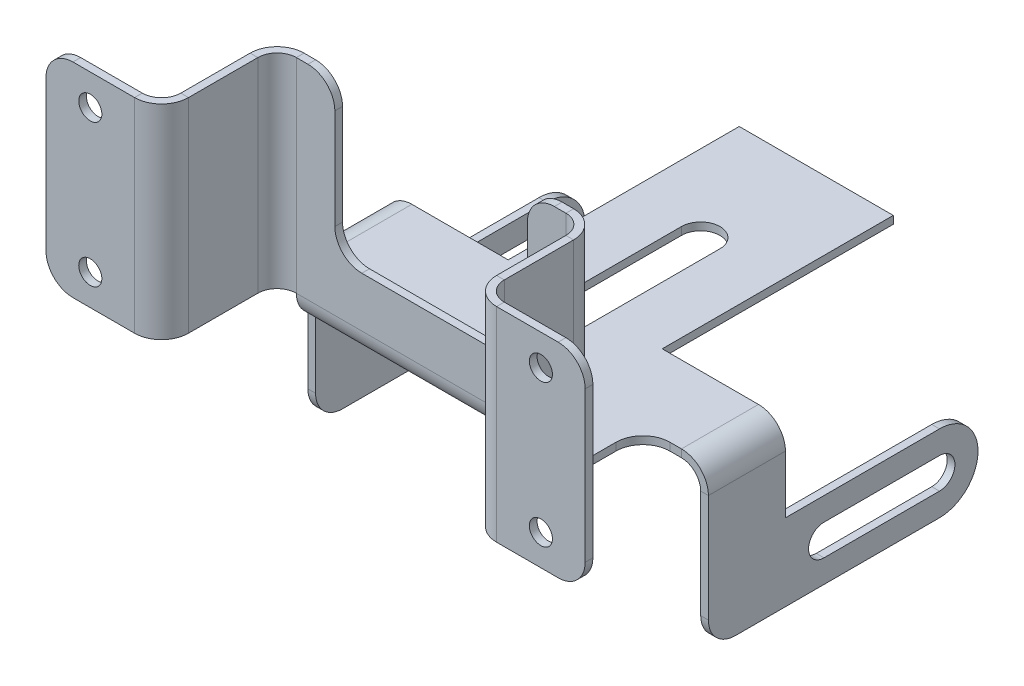
SolidWorks part; units mm, degrees
note: The reader was unsure of these and kept them because the rebuilt part matched: flange length of "边线-法兰1", "边线-法兰3", "边线-法兰4", "边线-法兰5".
ref_plane "前视基准面" through (0, 0, 0) normal (0, 0, 1) x (1, 0, 0)
ref_plane "上视基准面" through (0, 0, 0) normal (0, 1, 0) x (1, 0, 0)
ref_plane "右视基准面" through (0, 0, 0) normal (1, 0, 0) x (0, 0, -1)
other "Configuration Table"
sketch "草图1" plane through (0, 0, 0) normal (0, 0, 1) x (1, 0, 0)
  line L0 (-25, 0) -> (25, 0)
  dimension "D1" = 50
base flange "基体-法兰1" sketch "草图1" end condition mid plane depth 10 reverse direction no thickness 1 reverse thickness direction no bend radius 2.5
edge flange "边线-法兰1" sketch "草图8" flange angle 90 flange length 21 flange position material outside bend radius 2.5 thickness 1 parameters "D6"=10
sketch "草图8" plane through (-25, -1, 0) normal (-1, 0, 0) x (0, 0, -1)
  line L2 (-5, 0) -> (-5, 20)
  line L3 (-5, 20) -> (5, 20)
  line L4 (5, 20) -> (5, 0)
  line L7 (-5, 0) -> (5, 0) construction
  line L8 (-5, 0) -> (5, 0)
  dimension "D1" = 20
bend "边线折弯1" bend radius 2.5 bend angle 90 parameters "D5"=1
sketch "草图9" plane through (-26, 0, 0) normal (-1, 0, 0) x (0, 0, 1)
  line L0 (-5, -16) -> (-25, -16) construction
  line L1 (-5, -3.5) -> (-5, -21) construction
  line L2 (-5, -21) -> (-25, -21)
  line L3 (-5, -11) -> (-25, -11)
  line L4 (-5, -21) -> (5, -21) construction
  line L5 (-5, -11) -> (-5, -21)
  line L6 (-10, -16) -> (-25, -16) construction
  line L7 (-10, -18) -> (-25, -18)
  line L8 (-10, -14) -> (-25, -14)
  arc A0 (-5, -21) -> (-5, -11) centre (-5, -16) ccw construction
  arc A1 (-25, -11) -> (-25, -21) centre (-25, -16) ccw
  arc A2 (-10, -18) -> (-10, -14) centre (-10, -16) ccw
  arc A3 (-25, -14) -> (-25, -18) centre (-25, -16) ccw
  point P11 (-17.5, -16)
  dimension "D2" = 5
  dimension "D3" = 5
  dimension "D5" = 2
  dimension "D1" = 20
  dimension "D4" = 10
  dimension "D6" = 15
base flange "薄片1" sketch "草图9" thickness 1 reverse thickness direction no parameters "D1"=2.5
mirror "镜向1" about plane through (0, 0, 0) normal (1, 0, 0) of "薄片1", "边线-法兰1"
bend "镜向折弯1" bend radius 2.5 bend angle 90 parameters "D5"=2
sketch "草图12" plane through (0, -1, 0) normal (0, -1, 0) x (1, 0, 0)
  line L0 (-22.5, -5) -> (22.5, -5) construction
  line L1 (-10, -5) -> (10, -5)
  line L2 (-10, -5) -> (-10, -35)
  line L3 (-10, -35) -> (10, -35)
  line L4 (10, -5) -> (10, -35)
  line L5 (-10, -5) -> (10, -35) construction
  line L6 (-10, -35) -> (10, -5) construction
  line L7 (-22.5, 5) -> (22.5, 5) construction
  line L8 (-17.5, 15) -> (17.5, 15)
  line L9 (-17.5, 15) -> (-17.5, 5)
  line L10 (-17.5, 5) -> (17.5, 5)
  line L11 (17.5, 15) -> (17.5, 5)
  line L12 (-17.5, 15) -> (17.5, 5) construction
  line L13 (-17.5, 5) -> (17.5, 15) construction
  point P0 (0, -20)
  point P10 (0, 10)
  dimension "D1" = 30
  dimension "D2" = 20
  dimension "D3" = 35
  dimension "D4" = 10
base flange "薄片2" sketch "草图12" thickness 1 reverse thickness direction no parameters "D1"=2.5
edge flange "边线-法兰3" sketch "草图20" flange angle 90 flange length 30 flange position material inside bend radius 2.5 thickness 1 parameters "D6"=10
sketch "草图20" plane through (0, 0, 15) normal (0, 0, 1) x (1, 0, 0)
  line L2 (-17.5, 0) -> (-17.5, 29)
  line L3 (-17.5, 29) -> (17.5, 29)
  line L4 (17.5, 29) -> (17.5, 0)
  line L7 (17.5, 0) -> (-17.5, 0) construction
  line L8 (17.5, 0) -> (-17.5, 0)
bend "边线折弯3" bend radius 2.5 bend angle 90 parameters "D5"=3
sketch "草图21" plane through (0, 0, 15) normal (0, 0, 1) x (1, 0, 0)
  line L0 (17.5, 29) -> (-17.5, 29) construction
  line L1 (-12.5, 29) -> (12.5, 29)
  line L2 (-12.5, 29) -> (-12.5, 9)
  line L3 (-12.5, 9) -> (12.5, 9)
  line L4 (12.5, 29) -> (12.5, 9)
  line L5 (-12.5, 29) -> (12.5, 9) construction
  line L6 (-12.5, 9) -> (12.5, 29) construction
  point P0 (0, 19)
  dimension "D1" = 25
  dimension "D2" = 20
extrude "切除-拉伸1" cut sketch "草图21" against normal up to next
edge flange "边线-法兰4" sketch "草图24" flange angle 90 flange length 15 flange position bend outside bend radius 2.5 thickness 1 parameters "D6"=10
sketch "草图24" plane through (-17.5, 0, 15) normal (-1, 0, 0) x (0, -1, 0)
  line L2 (-29, 0) -> (-29, 14)
  line L3 (-29, 14) -> (-2.5, 14)
  line L4 (-2.5, 14) -> (-2.5, 0)
  line L7 (-29, 0) -> (-2.5, 0) construction
  line L8 (-29, 0) -> (-2.5, 0)
bend "边线折弯4" bend radius 2.5 bend angle 90 parameters "D5"=4
edge flange "边线-法兰5" sketch "草图27" flange angle 90 flange length 15 flange position material outside bend radius 2.5 thickness 1 parameters "D6"=10
sketch "草图27" plane through (-21, 0, 29) normal (0, 0, 1) x (0, 1, 0)
  line L0 (2.5, 0) -> (29, 0) construction
  line L1 (2.5, 0) -> (29, 0)
  line L2 (2.5, 0) -> (2.5, 14)
  line L3 (2.5, 14) -> (29, 14)
  line L4 (29, 14) -> (29, 0)
bend "边线折弯5" bend radius 2.5 bend angle 90 parameters "D5"=5
sketch "草图28" plane through (0, 0, 30) normal (0, 0, 1) x (1, 0, 0)
  line L0 (-23.5, 29) -> (-35, 29) construction
  line L1 (-35, 15.75) -> (-23.5, 15.75) construction
  line L2 (-35, 29) -> (-35, 2.5) construction
  line L3 (-23.5, 29) -> (-23.5, 2.5) construction
  circle A0 centre (-29.25, 25) radius 1.5
  circle A1 centre (-29.25, 6.5) radius 1.5
  point P5 (-29.25, 29)
  dimension "D1" = 3
  dimension "D2" = 4
extrude "切除-拉伸2" cut sketch "草图28" against normal up to next
mirror "镜向2" about plane through (0, 0, 0) normal (1, 0, 0) of "切除-拉伸2", "边线-法兰4", "边线-法兰5"
bend "镜向折弯2" bend radius 2.5 bend angle 90 parameters "D5"=6
bend "镜向折弯3" bend radius 2.5 bend angle 90 parameters "D5"=7
fillet "圆角1" radius 3.5 12 edges at (17.5, -0.5, 5) (-17.5, -0.5, 5) (12.5, 29, 14.5) (12.5, 9, 14.5) (-12.5, 9, 14.5) (-12.5, 29, 14.5) (-35, 2.5, 29.5) (-35, 29, 29.5) (35, 29, 29.5) (35, 2.5, 29.5) (-25.5, -21, 5) (25.5, -21, 5)
sketch "草图29" plane through (0, -1, 0) normal (0, -1, 0) x (1, 0, 0)
  line L0 (0, 0) -> (0, -20) construction
  line L1 (2.5, 0) -> (2.5, -20)
  line L2 (-2.5, 0) -> (-2.5, -20)
  arc A0 (2.5, 0) -> (-2.5, 0) centre (0, 0) ccw
  arc A1 (-2.5, -20) -> (2.5, -20) centre (0, -20) ccw
  point P2 (0, -10)
  point P7 (0, 0)
  dimension "D1" = 20
  dimension "D2" = 5
extrude "切除-拉伸3" cut sketch "草图29" against normal up to next
sketch "折弯-线1" [suppressed] plane through (0, 0, 0) normal (0, 1, 0) x (1, 0, 0)
sketch "边界框1" [suppressed] plane through (0, 0, 0) normal (0, 1, 0) x (1, 0, 0)
sheet metal parameters "钣金6" thickness 1 parameters "D1"=2.5
flat pattern "平板型式6" [suppressed]
sketch "折弯-线2" plane through (0, 0, 0) normal (0, 1, 0) x (1, 0, 0)
sketch "边界框2" [suppressed] plane through (0, 0, 0) normal (0, 1, 0) x (1, 0, 0)
sheet metal parameters "钣金7" thickness 1 parameters "D1"=2.5
flat pattern "平板型式6" [suppressed]
sketch "折弯-线2" plane through (0, 0, 0) normal (0, 1, 0) x (1, 0, 0)
sketch "边界框2" [suppressed] plane through (0, 0, 0) normal (0, 1, 0) x (1, 0, 0)
bend of the flat pattern "展平-<边线折弯1>1"
sheet metal parameters "钣金8" thickness 1 parameters "D1"=2.5
flat pattern "平板型式8" [suppressed]
sketch "折弯-线3" plane through (0, 0, 0) normal (0, 1, 0) x (1, 0, 0)
sketch "边界框3" [suppressed] plane through (0, 0, 0) normal (0, 1, 0) x (1, 0, 0)
bend of the flat pattern "展平-<边线折弯1>2"
sheet metal parameters "钣金9" thickness 1 parameters "D1"=2.5
flat pattern "平板型式8" [suppressed]
sketch "折弯-线3" plane through (0, 0, 0) normal (0, 1, 0) x (1, 0, 0)
sketch "边界框3" [suppressed] plane through (0, 0, 0) normal (0, 1, 0) x (1, 0, 0)
bend of the flat pattern "展平-<边线折弯1>2"
bend of the flat pattern "展平-<镜向折弯1>1"
sheet metal parameters "钣金10" thickness 1 parameters "D1"=2.5
flat pattern "平板型式10" [suppressed]
sketch "折弯-线4" plane through (0, 0, 0) normal (0, 1, 0) x (1, 0, 0)
sketch "边界框4" [suppressed] plane through (0, 0, 0) normal (0, 1, 0) x (1, 0, 0)
bend of the flat pattern "展平-<边线折弯1>3"
bend of the flat pattern "展平-<镜向折弯1>2"
sheet metal parameters "钣金12" thickness 1 parameters "D1"=2.5
flat pattern "平板型式10" [suppressed]
sketch "折弯-线4" plane through (0, 0, 0) normal (0, 1, 0) x (1, 0, 0)
sketch "边界框4" [suppressed] plane through (0, 0, 0) normal (0, 1, 0) x (1, 0, 0)
bend of the flat pattern "展平-<边线折弯1>3"
bend of the flat pattern "展平-<镜向折弯1>2"
bend of the flat pattern "展平-<边线折弯3>1"
sheet metal parameters "钣金13" thickness 1 parameters "D1"=2.5
flat pattern "平板型式10" [suppressed]
sketch "折弯-线4" plane through (0, 0, 0) normal (0, 1, 0) x (1, 0, 0)
sketch "边界框4" [suppressed] plane through (0, 0, 0) normal (0, 1, 0) x (1, 0, 0)
bend of the flat pattern "展平-<边线折弯1>3"
bend of the flat pattern "展平-<镜向折弯1>2"
bend of the flat pattern "展平-<边线折弯3>1"
sheet metal parameters "钣金14" thickness 1 parameters "D1"=2.5
flat pattern "平板型式10" [suppressed]
sketch "折弯-线4" plane through (0, 0, 0) normal (0, 1, 0) x (1, 0, 0)
sketch "边界框4" [suppressed] plane through (0, 0, 0) normal (0, 1, 0) x (1, 0, 0)
bend of the flat pattern "展平-<边线折弯1>3"
bend of the flat pattern "展平-<镜向折弯1>2"
bend of the flat pattern "展平-<边线折弯3>1"
bend of the flat pattern "展平-<边线折弯4>1"
sheet metal parameters "钣金15" thickness 1 parameters "D1"=2.5
flat pattern "平板型式10" [suppressed]
sketch "折弯-线4" plane through (0, 0, 0) normal (0, 1, 0) x (1, 0, 0)
sketch "边界框4" [suppressed] plane through (0, 0, 0) normal (0, 1, 0) x (1, 0, 0)
bend of the flat pattern "展平-<边线折弯1>3"
bend of the flat pattern "展平-<镜向折弯1>2"
bend of the flat pattern "展平-<边线折弯3>1"
bend of the flat pattern "展平-<边线折弯4>1"
bend of the flat pattern "展平-<边线折弯5>1"
sheet metal parameters "钣金16" thickness 1 parameters "D1"=2.5
flat pattern "平板型式10" [suppressed]
sketch "折弯-线4" plane through (0, 0, 0) normal (0, 1, 0) x (1, 0, 0)
sketch "边界框4" [suppressed] plane through (0, 0, 0) normal (0, 1, 0) x (1, 0, 0)
bend of the flat pattern "展平-<边线折弯1>3"
bend of the flat pattern "展平-<镜向折弯1>2"
bend of the flat pattern "展平-<边线折弯3>1"
bend of the flat pattern "展平-<边线折弯4>1"
bend of the flat pattern "展平-<边线折弯5>1"
sheet metal parameters "钣金17" thickness 1 parameters "D1"=2.5
flat pattern "平板型式10"
sketch "折弯-线4" plane through (0, 0, 0) normal (0, 1, 0) x (1, 0, 0)
  line L0 (33.5686, -16.2124) -> (33.5686, -42.7124) construction
  line L1 (19.8562, -16.2124) -> (19.8562, -42.7124) construction
  line L2 (-33.5686, -42.7124) -> (-33.5686, -16.2124) construction
  line L3 (-19.8562, -42.7124) -> (-19.8562, -16.2124) construction
  line L4 (17.5, -13.8562) -> (-17.5, -13.8562) construction
  line L5 (24.8562, 5) -> (24.8562, -5) construction
  line L6 (-24.8562, -5) -> (-24.8562, 5) construction
  line L7 (33.5686, -16.2124) -> (33.5686, -42.7124) construction
  line L8 (19.8562, -16.2124) -> (19.8562, -42.7124) construction
  line L9 (-33.5686, -42.7124) -> (-33.5686, -16.2124) construction
  line L10 (-19.8562, -42.7124) -> (-19.8562, -16.2124) construction
  line L11 (17.5, -13.8562) -> (-17.5, -13.8562) construction
  line L12 (24.8562, 5) -> (24.8562, -5) construction
  line L13 (-24.8562, -5) -> (-24.8562, 5) construction
sketch3d "边界框4" [suppressed]
  line L0 (-22.4248, -37.7123, 0) -> (72.4248, -37.7124, 0) construction
  line L1 (-22.4247, 40.0001, 0) -> (72.4249, 39.9999, 0) construction
  line L2 (-22.4248, -37.7123, 0) -> (-22.4247, 40.0001, 0) construction
  line L3 (72.4248, -37.7124, 0) -> (72.4249, 39.9999, 0) construction
bend of the flat pattern "展平-<边线折弯1>3"
bend of the flat pattern "展平-<镜向折弯1>2"
bend of the flat pattern "展平-<边线折弯3>1"
bend of the flat pattern "展平-<边线折弯4>1"
bend of the flat pattern "展平-<边线折弯5>1"
bend of the flat pattern "展平-<镜向折弯2>1"
bend of the flat pattern "展平-<镜向折弯3>1"
sheet metal parameters "钣金18" thickness 1 parameters "D1"=2.5
flat pattern "平板型式10"
sketch "折弯-线4" plane through (0, 0, 0) normal (0, 1, 0) x (1, 0, 0)
  line L0 (33.5686, -16.2124) -> (33.5686, -42.7124) construction
  line L1 (19.8562, -16.2124) -> (19.8562, -42.7124) construction
  line L2 (-33.5686, -42.7124) -> (-33.5686, -16.2124) construction
  line L3 (-19.8562, -42.7124) -> (-19.8562, -16.2124) construction
  line L4 (17.5, -13.8562) -> (-17.5, -13.8562) construction
  line L5 (24.8562, 5) -> (24.8562, -5) construction
  line L6 (-24.8562, -5) -> (-24.8562, 5) construction
  line L7 (33.5686, -16.2124) -> (33.5686, -42.7124) construction
  line L8 (19.8562, -16.2124) -> (19.8562, -42.7124) construction
  line L9 (-33.5686, -42.7124) -> (-33.5686, -16.2124) construction
  line L10 (-19.8562, -42.7124) -> (-19.8562, -16.2124) construction
  line L11 (17.5, -13.8562) -> (-17.5, -13.8562) construction
  line L12 (24.8562, 5) -> (24.8562, -5) construction
  line L13 (-24.8562, -5) -> (-24.8562, 5) construction
sketch3d "边界框4" [suppressed]
  line L0 (-22.4248, -37.7123, 0) -> (72.4248, -37.7124, 0) construction
  line L1 (-22.4247, 40.0001, 0) -> (72.4249, 39.9999, 0) construction
  line L2 (-22.4248, -37.7123, 0) -> (-22.4247, 40.0001, 0) construction
  line L3 (72.4248, -37.7124, 0) -> (72.4249, 39.9999, 0) construction
bend of the flat pattern "展平-<边线折弯1>3"
bend of the flat pattern "展平-<镜向折弯1>2"
bend of the flat pattern "展平-<边线折弯3>1"
bend of the flat pattern "展平-<边线折弯4>1"
bend of the flat pattern "展平-<边线折弯5>1"
bend of the flat pattern "展平-<镜向折弯2>1"
bend of the flat pattern "展平-<镜向折弯3>1"
